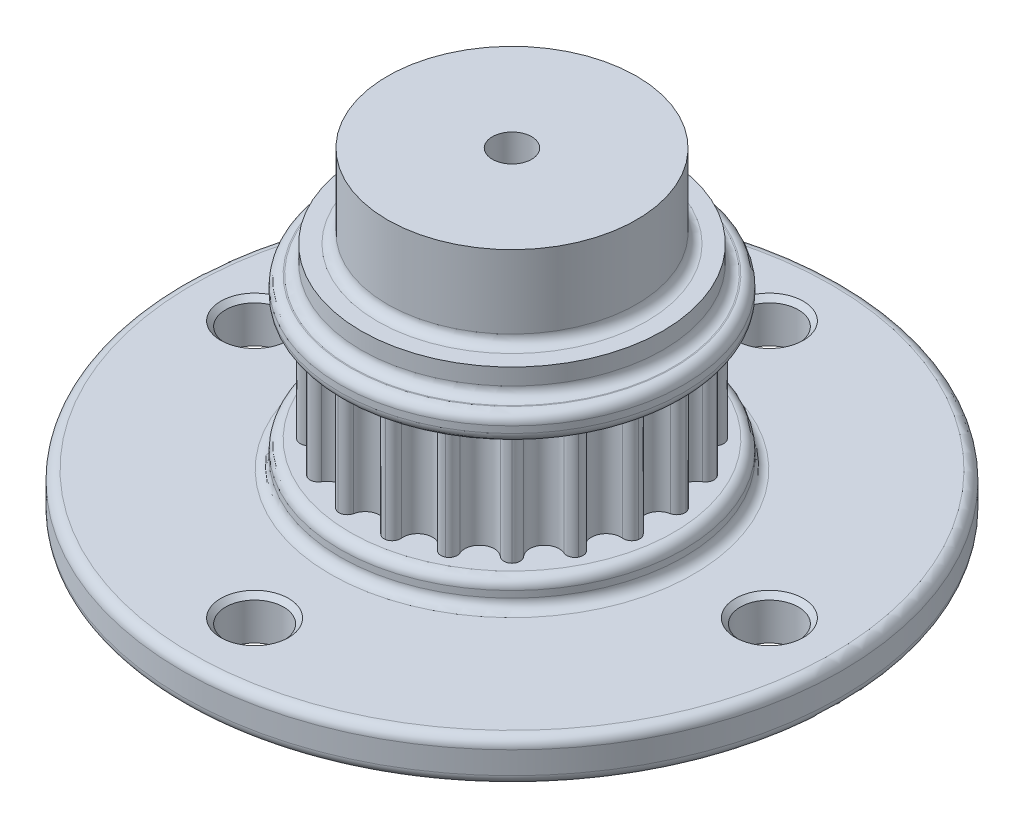
SolidWorks part; units mm, degrees
ref_plane "Front Plane" through (0, 0, 0) normal (0, 0, 1) x (1, 0, 0)
ref_plane "Top Plane" through (0, 0, 0) normal (0, 1, 0) x (1, 0, 0)
ref_plane "Right Plane" through (0, 0, 0) normal (1, 0, 0) x (0, 0, -1)
sketch "Sketch1" plane through (0, 0, 0) normal (0, 1, 0) x (1, 0, 0)
  line L0 (0, 0) -> (0, 9.1676) construction
  line L1 (0, 0) -> (2.731, 8.405) construction
  circle A0 centre (0, 0) radius 9.1676 construction
  circle A1 centre (0, 0) radius 7.9476 construction
  circle A2 centre (0, 8.8376) radius 0.89 construction
  circle A5 centre (2.731, 8.405) radius 0.89 construction
  arc A6 (0, 7.9476) -> (0.8721, 8.6598) centre (0, 8.8376) ccw
  arc A7 (0.8721, 8.6598) -> (1.4405, 9.0537) centre (1.362, 8.5599) cw
  arc A8 (1.4277, 9.0557) -> (1.8466, 8.5054) centre (1.3498, 8.5618) cw
  arc A9 (2.4559, 7.5586) -> (1.8466, 8.5054) centre (2.731, 8.405) cw
  arc A10 (1.4405, 9.0537) -> (1.4277, 9.0557) centre (0, 0) cw
  arc A11 (0, 7.9476) -> (2.4559, 7.5586) centre (0, 0) ccw
  dimension "D1" = 18.3352
  dimension "D3" = 1.78
  dimension "D4" = 0.5
  dimension "D2" = 1.22
  dimension "D5" = 18
extrude "Boss-Extrude1" add sketch "Sketch1" along normal mid plane 7.112 contours A6 A11 A9 A8 A7 region at (0.0089, 0, -0.0564)
ref_axis "Axis1" through (0, 3.3, 0) along (0, -1, 0)
pattern_circular "CirPattern1" count 20 over 360 about axis through (0, 3.3, 0) along (0, -1, 0) of "Boss-Extrude1"
sketch "Sketch2" plane through (0, 0, 0) normal (1, 0, 0) x (0, 0, -1)
  line L10 (0, 3.5) -> (10.3423, 3.5) construction
  line L11 (0, 3.5) -> (0, 5.0875) construction
  line L12 (0, 5.0875) -> (10.3423, 5.0875)
  line L15 (10.3423, 3.5) -> (10.3423, 5.0875) construction
  line L20 (0, 3.3) -> (0, -3.3) construction
  line L22 (10.3423, 5.0875) -> (0, 5.0875) construction
  line L23 (10.3423, 5.0875) -> (10.3423, 3.5)
  line L24 (10.3423, 3.5) -> (0, 3.5)
  line L25 (0, 5.0875) -> (0, 3.5)
  dimension "D1" = 1.5875
  dimension "D2" = 10.3423
  dimension "D3" = 3.5
revolve "Revolve3" add sketch "Sketch2" angle 360 about axis through (0, 3.3, 0) along (0, -1, 0) region at (0, 4.2937, -5.1712)
mirror "Mirror1" about plane through (0, 0, 0) normal (0, 1, 0) of "Revolve3"
sketch "Sketch9" plane through (0, -5.0875, 0) normal (0, -1, 0) x (1, 0, 0)
  circle A0 centre (0, 0) radius 19.8438
  circle A1 centre (0, 0) radius 1.5
  dimension "D1" = 3
  dimension "D2" = 39.6875
extrude "Boss-Extrude2" add sketch "Sketch9" along normal blind 2.54
sketch "Sketch3" plane through (0, 0, 0) normal (0, 1, 0) x (1, 0, 0)
  circle A0 centre (-15.5, 0) radius 1.7462
  circle A3 centre (0, 15.5) radius 1.7462
  circle A4 centre (15.5, 0) radius 1.7463
  circle A5 centre (0, -15.5) radius 1.7462
  dimension "D3" = 3.4925
  dimension "D1" = 15.5
  dimension "D4" = 4
extrude "Cut-Extrude1" cut sketch "Sketch3" against normal through all both and the other way through all
ref_axis "Axis2" through (-15.5, -7.6275, 0) along (0, 1, 0)
sketch "Sketch6" plane through (0, 0, 0) normal (0, 0, 1) x (1, 0, 0)
  line L0 (-19.1322, -3.5) -> (-11.8678, -3.5) construction
  line L1 (-5.7956, -3.5) -> (-6.4824, -3.5) construction
  line L2 (-11.8678, -3.5) -> (-15.5, -7.1322)
  line L3 (-15.5, -7.1322) -> (-19.1322, -3.5) construction
  line L4 (-18.548, -4.0842) -> (-12.452, -4.0842) construction
  line L5 (-17.2462, -3.998) -> (-13.7538, -3.998) construction
  line L8 (-15.5, -7.1322) -> (-15.5, -3.5)
  line L9 (-15.5, -3.5) -> (-11.8678, -3.5)
  line L10 (-15.5, -7.6275) -> (-15.5, -5.0875) construction
  line L12 (-17.2462, -5.0875) -> (-17.2462, -7.6275) construction
  line L13 (-13.7538, -7.6275) -> (-13.7538, -5.0875) construction
  point P2 (-15.5, -3.998)
  dimension "D1" = 6.096
  dimension "D2" = 0.5842
revolve "Cut-Revolve2" cut sketch "Sketch6" angle 360 about axis through (-15.5, -7.6275, 0) along (0, 1, 0)
pattern_circular "CirPattern2" count 4 over 360 about axis through (0, 3.3, 0) along (0, -1, 0) of "Cut-Revolve2"
sketch "Sketch10" plane through (0, 0, 0) normal (1, 0, 0) x (0, 0, -1)
  line L1 (1.1822, 6.675) -> (7.5, 6.675) construction
  line L2 (1.1822, 6.675) -> (1.1822, 11.675)
  line L3 (1.1822, 11.675) -> (7.5, 11.675)
  line L4 (7.5, 6.675) -> (7.5, 11.675)
  line L5 (0, 0) -> (0, 11.675) construction
  line L6 (10.3423, 5.0875) -> (-10.3423, 5.0875) construction
  line L7 (1.1822, 6.675) -> (9.0875, 6.675) construction
  line L8 (1.1822, 6.675) -> (1.1822, 5.0875)
  line L9 (1.1822, 5.0875) -> (9.0875, 5.0875)
  line L10 (9.0875, 6.675) -> (9.0875, 5.0875)
  line L11 (7.5, 6.675) -> (9.0875, 6.675)
  line L12 (0, 11.675) -> (1.1822, 11.675) construction
  dimension "D1" = 2.3644
  dimension "D2" = 5
  dimension "D3" = 1.5875
  dimension "D4" = 1.5875
  dimension "D5" = 15
revolve "Revolve4" add sketch "Sketch10" angle 360 about L5
fillet "Fillet1" radius 0.5953 8 edges at (0, 5.0875, 10.3423) (0, 3.5, 10.3423) (0, -7.6275, -19.8438) (0, -5.0875, -19.8438) (0, 6.675, -7.5) (0, 5.0875, -9.0875) (0, -3.5, 10.3423) (0, -5.0875, 10.3423)
sketch "Sketch11" plane through (0, -5.0875, 0) normal (0, -1, 0) x (1, 0, 0)
  circle A0 centre (0, 0) radius 1.5
  dimension "D1" = 3
extrude "Cut-Extrude2" cut sketch "Sketch11" against normal blind 6
sketch "Sketch12" plane through (0, 11.675, 0) normal (0, 1, 0) x (1, 0, 0)
  line L0 (-3.175, 0) -> (0, 0) construction
  line L1 (0, 0) -> (3.175, 0) construction
  circle A0 centre (-3.175, 0) radius 1.143
  circle A1 centre (3.175, 0) radius 1.143
  dimension "D1" = 2.286
  dimension "D2" = 3.175
extrude "Cut-Extrude3" [suppressed] cut sketch "Sketch12" against normal blind 15.875
equation "\"TEETH_NUM\"= 20"
equation "\"TOOTH_PITCH\"= 3mm"
equation "\"PITCH_LINE_OFFSET\"= .015in"
equation "\"DIAMETER_PER_GROOVE\"= \"OUTSIDE_DIAMETER\" / \"TEETH_NUM\" * 1in"
equation "\"PITCH_DIAMETER\"= ( ( \"TEETH_NUM\" * 3 - 1.31 ) / 3.1415 + .415 ) * 1mm"
equation "\"OUTSIDE_DIAMETER\"= \"PITCH_DIAMETER\" - \"PITCH_LINE_OFFSET\" * 2"
equation "\"D1@Sketch1\"=\"OUTSIDE_DIAMETER\""
equation "\"TOOTH_HEIGHT\"= 1.22mm"
equation "\"D2@Sketch1\"=\"TOOTH_HEIGHT\""
equation "\"TOOTH_DIAMETER\"= 1.78mm"
equation "\"INTERNAL_RADIUS\"= .5mm"
equation "\"D3@Sketch1\"=\"TOOTH_DIAMETER\""
equation "\"D5@Sketch1\"=360 / \"TEETH_NUM\""
equation "\"D4@Sketch1\"=\"INTERNAL_RADIUS\""
equation "\"D1@CirPattern1\"=\"TEETH_NUM\""
equation "\"BELT_GAP\"= 7mm"
equation "\"D2@Sketch2\"=\"PITCH_DIAMETER\"/2+1/32"
equation "\"D3@Sketch2\"=\"BELT_GAP\"/2"
